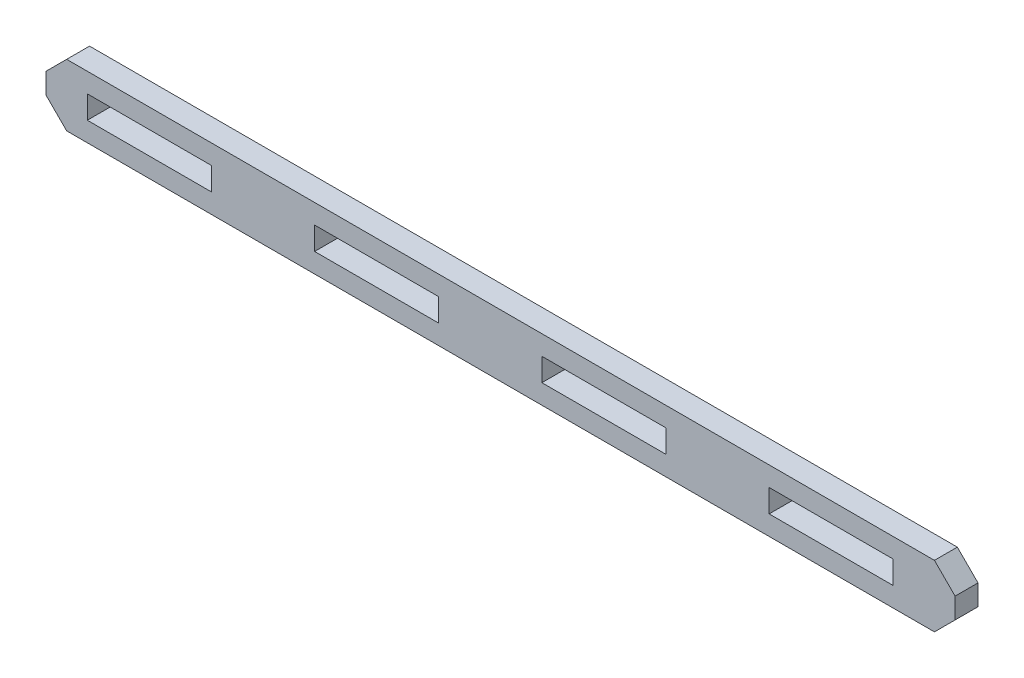
SolidWorks part; units mm, degrees
ref_plane "Front Plane" through (0, 0, 0) normal (0, 0, 1) x (1, 0, 0)
ref_plane "Top Plane" through (0, 0, 0) normal (0, 1, 0) x (1, 0, 0)
ref_plane "Right Plane" through (0, 0, 0) normal (1, 0, 0) x (0, 0, -1)
sketch "Sketch2" plane through (0, 0, 0) normal (0, 0, 1) x (1, 0, 0)
  line L0 (120.8548, 10.416) -> (120.8548, 4.876)
  line L5 (60.8548, 15.146) -> (270.8548, 15.146)
  line L39 (55.8548, 10.146) -> (55.8548, 5.146)
  line L40 (60.8548, 0.146) -> (270.8548, 0.146)
  line L41 (275.8548, 10.146) -> (275.8548, 5.146)
  line L42 (65.8548, 10.416) -> (95.8548, 10.416)
  line L43 (65.8548, 10.416) -> (65.8548, 4.876)
  line L44 (65.8548, 4.876) -> (95.8548, 4.876)
  line L45 (95.8548, 10.416) -> (95.8548, 4.876)
  line L46 (120.8548, 10.416) -> (150.8548, 10.416)
  line L47 (150.8548, 10.416) -> (150.8548, 4.876)
  line L48 (120.8548, 4.876) -> (150.8548, 4.876)
  line L49 (175.8548, 10.416) -> (175.8548, 4.876)
  line L50 (175.8548, 10.416) -> (205.8548, 10.416)
  line L51 (205.8548, 10.416) -> (205.8548, 4.876)
  line L52 (175.8548, 4.876) -> (205.8548, 4.876)
  line L53 (230.8548, 10.416) -> (230.8548, 4.876)
  line L54 (230.8548, 10.416) -> (260.8548, 10.416)
  line L55 (260.8548, 10.416) -> (260.8548, 4.876)
  line L56 (230.8548, 4.876) -> (260.8548, 4.876)
  line L57 (55.8548, 10.146) -> (60.8548, 15.146)
  line L58 (55.8548, 5.146) -> (60.8548, 0.146)
  line L59 (270.8548, 0.146) -> (275.8548, 5.146)
  line L60 (270.8548, 15.146) -> (275.8548, 10.146)
  point P0 (55.8548, 15.146)
  point P1 (275.8548, 0.146)
  point P2 (55.8548, 0.146)
  point P3 (275.8548, 15.146)
  dimension "D1" = 220
  dimension "D2" = 15
  dimension "D3" = 4.73
  dimension "D4" = 5.54
  dimension "D5" = 30
  dimension "D6" = 10
  dimension "D7" = 4
extrude "Boss-Extrude1" add sketch "Sketch2" along normal blind 5.54
